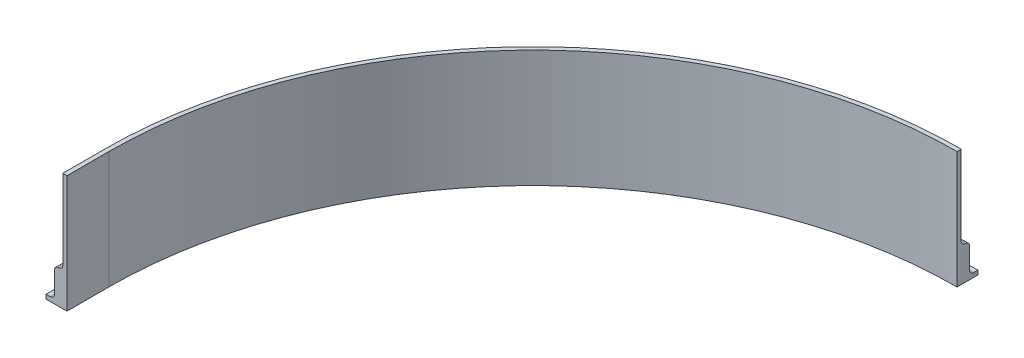
SolidWorks part; units mm, degrees
material "AISI 4340 Steel, annealed"
ref_plane "Front Plane" through (0, 0, 0) normal (0, 0, 1) x (1, 0, 0)
ref_plane "Top Plane" through (0, 0, 0) normal (0, 1, 0) x (1, 0, 0)
ref_plane "Right Plane" through (0, 0, 0) normal (1, 0, 0) x (0, 0, -1)
sketch "Sketch1" plane through (0, 0, 0) normal (0, 1, 0) x (1, 0, 0)
  line L3 (0, 0) -> (25, 0) construction
  line L4 (531, 531) -> (531, 506)
  line L5 (0, 0) -> (0, -50)
  line L6 (0, -50) -> (25, -50)
  line L7 (25, -50) -> (25, 0)
  arc A0 (0, 0) -> (531, 531) centre (531, 0) cw
  arc A1 (25, 0) -> (531, 506) centre (531, 0) cw
  dimension "D1" = 531
  dimension "D2" = 25
  dimension "D3" = 50
extrude "Bottom level" add sketch "Sketch1" along normal blind 5
sketch "Sketch2" plane through (0, 5, 0) normal (0, 1, 0) x (1, 0, 0)
  line L4 (10, 0) -> (25, 0) construction
  line L5 (531, 521) -> (531, 506)
  line L6 (25, 0) -> (25, -50)
  line L7 (531, 521) -> (581, 521) construction
  line L8 (531, 506) -> (581, 506) construction
  line L9 (25, -50) -> (10, -50)
  line L10 (0, -50) -> (25, -50) construction
  line L11 (10, -50) -> (10, 0)
  arc A0 (531, 506) -> (25, 0) centre (531, 0) ccw construction
  arc A1 (531, 506) -> (25, 0) centre (531, 0) ccw
  arc A2 (531, 521) -> (10, 0) centre (531, 0) ccw
  dimension "D1" = 15
extrude "Mid level" add sketch "Sketch2" along normal blind 35
sketch "Sketch3" plane through (0, 40, 0) normal (0, 1, 0) x (1, 0, 0)
  line L6 (25, -50) -> (25, 0) construction
  line L7 (25, -50) -> (25, 0)
  line L8 (20, -50) -> (20, 0)
  line L10 (20, -50) -> (25, -50)
  line L11 (531, 511) -> (531, 506)
  arc A3 (531, 506) -> (25, 0) centre (531, 0) ccw construction
  arc A4 (531, 506) -> (25, 0) centre (531, 0) ccw
  arc A5 (531, 511) -> (20, 0) centre (531, 0) ccw
  dimension "D1" = 5
extrude "Guard rail" add sketch "Sketch3" along normal blind 100
fillet "Rounding" radius 5 6 edges at (162.5974, 40, -368.4026) (162.5974, 5, -368.4026) (10, 40, 25) (10, 5, 25) (20, 40, 25) (169.6684, 40, -361.3316)
